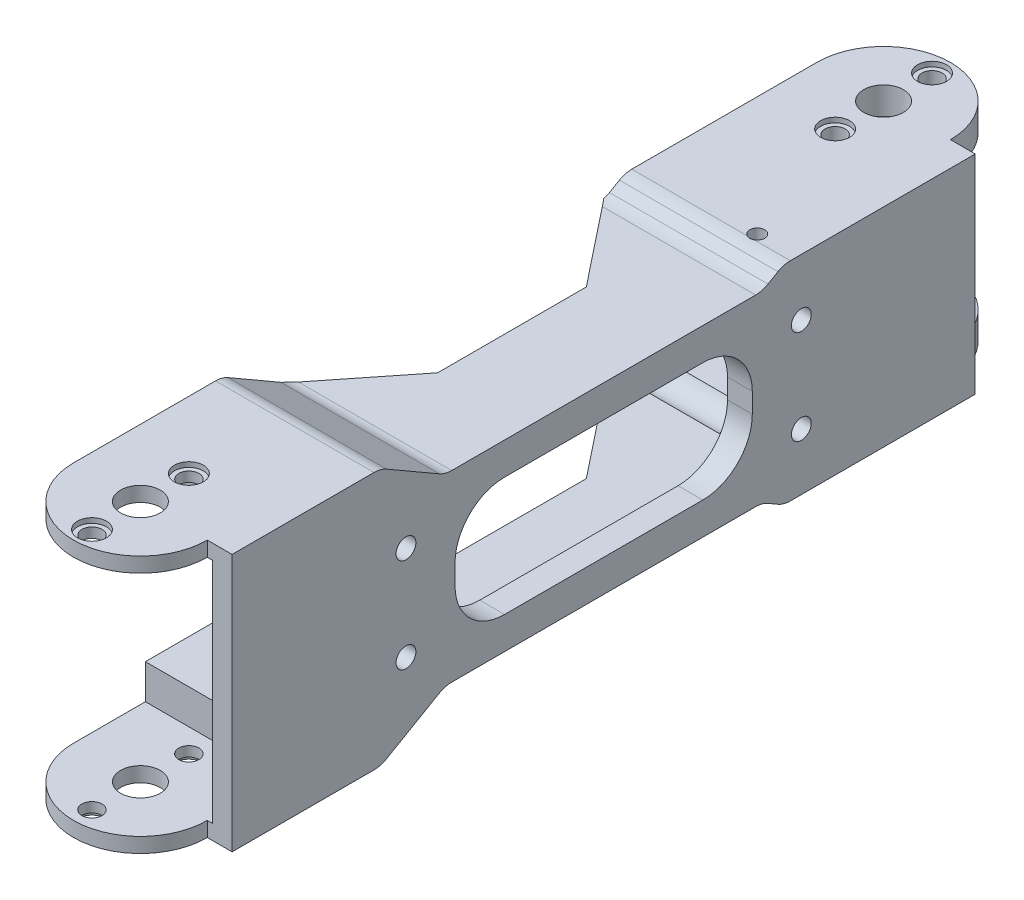
SolidWorks part; units mm, degrees
material "Custom Plastic"
ref_plane "Front Plane" through (0, 0, 0) normal (0, 0, 1) x (1, 0, 0)
ref_plane "Top Plane" through (0, 0, 0) normal (0, 1, 0) x (1, 0, 0)
ref_plane "Right Plane" through (0, 0, 0) normal (1, 0, 0) x (0, 0, -1)
sketch "Sketch1" plane through (0, 0, 0) normal (0, 1, 0) x (1, 0, 0)
  line L0 (0, 75) -> (0, -75) construction
  line L2 (-13.5, 75) -> (-13.5, -75)
  line L4 (13.5, 75) -> (13.5, -75)
  arc A0 (13.5, 75) -> (-13.5, 75) centre (0, 75) ccw
  arc A1 (-13.5, -75) -> (13.5, -75) centre (0, -75) ccw
  point P5 (0, 0)
  dimension "D1" = 150
  dimension "D2" = 27
extrude "Boss-Extrude1" add sketch "Sketch1" along normal mid plane 52
sketch "Sketch3" plane through (-13.5, 0, 0) normal (-1, 0, 0) x (0, 0, 1)
  line L0 (-45, 26) -> (-32.0096, 18.5)
  line L1 (-75, 26) -> (75, 26) construction
  line L2 (-32.0096, 18.5) -> (32.0096, 18.5)
  line L3 (32.0096, 18.5) -> (45, 26)
  line L4 (45, 26) -> (-45, 26)
  line L5 (-75, 26) -> (-75, -26) construction
  point P6 (0, 18.5)
  point P7 (0, 26)
  dimension "D1" = 7.5
  dimension "D2" = 30
  dimension "D3" = 30
extrude "Cut-Extrude1" cut sketch "Sketch3" against normal through all both and the other way through all
mirror "Mirror1" about plane through (0, 0, 0) normal (0, 1, 0) of "Cut-Extrude1"
sketch "Sketch4" plane through (-13.5, 0, 0) normal (-1, 0, 0) x (0, 0, 1)
  line L0 (-88.5, 26) -> (-88.5, -26) construction
  line L1 (60.5, 23) -> (88.5, 23)
  line L2 (-88.5, 15) -> (-60.5, 15)
  line L3 (-88.5, 15) -> (-88.5, 9)
  line L4 (-88.5, 9) -> (-60.5, 9)
  line L5 (-60.5, 15) -> (-60.5, 9)
  line L6 (-88.5, -15) -> (-60.5, -15)
  line L7 (-88.5, -15) -> (-88.5, -9)
  line L8 (-88.5, -9) -> (-60.5, -9)
  line L9 (-60.5, -15) -> (-60.5, -9)
  line L10 (60.5, 23) -> (60.5, 17)
  line L11 (60.5, 17) -> (88.5, 17)
  line L12 (88.5, 23) -> (88.5, 17)
  line L13 (60.5, -17) -> (88.5, -17)
  line L14 (60.5, -17) -> (60.5, -23)
  line L15 (60.5, -23) -> (88.5, -23)
  line L16 (88.5, -17) -> (88.5, -23)
  line L18 (88.5, -26) -> (88.5, 26) construction
  line L19 (-60.5, 9) -> (-60.5, -9) construction
  line L20 (60.5, 17) -> (60.5, -17) construction
  point P20 (-60.5, 0)
  point P21 (60.5, 0)
  dimension "D1" = 28
  dimension "D2" = 6
  dimension "D3" = 18
  dimension "D4" = 34
extrude "Cut-Extrude2" cut sketch "Sketch4" against normal through all both
sketch "Sketch5" plane through (-13.5, 0, 0) normal (-1, 0, 0) x (0, 0, 1)
  line L1 (-88.5, 15) -> (60.5, 15)
  line L2 (-88.5, 15) -> (-88.5, -15)
  line L3 (-88.5, -15) -> (60.5, -15)
  line L5 (-88.5, -15) -> (-88.5, -26) construction
  line L6 (-60.5, 15) -> (-75, 15) construction
  line L7 (-75, -15) -> (-60.5, -15) construction
  line L8 (60.5, 15) -> (60.5, 23)
  line L9 (88.5, -23) -> (60.5, -23)
  line L10 (88.5, -23) -> (88.5, 23)
  line L11 (88.5, 23) -> (60.5, 23)
  line L12 (60.5, -23) -> (60.5, -15)
  line L13 (60.5, -17) -> (60.5, -23) construction
  line L15 (75, 23) -> (88.5, 23) construction
  line L16 (60.5, -23) -> (75, -23) construction
  line L17 (88.5, -17) -> (88.5, 17) construction
extrude "Cut-Extrude3" cut sketch "Sketch5" against normal offset from surface (22 mm away) 5 contours L2 L3 L12 L9 L10 L11 L8 L1 up to face at (13.5, 0, 0)
sketch "Sketch6" plane through (8.5, 0, 0) normal (-1, 0, 0) x (0, 0, 1)
  line L0 (60.5, -15) -> (-60.5, -15) construction
  line L1 (85.4881, 17) -> (60.5, 17)
  line L2 (85.4881, 17) -> (85.4881, -15)
  line L3 (85.4881, -15) -> (60.5, -15)
  line L4 (60.5, 17) -> (60.5, -15)
  line L5 (60.5, -15) -> (60.5, -23) construction
  line L7 (60.5, 17) -> (75, 17) construction
extrude "Cut-Extrude4" cut sketch "Sketch6" against normal through all
sketch "Sketch7" plane through (8.5, 0, 0) normal (-1, 0, 0) x (0, 0, 1)
  line L1 (-85.4881, 9) -> (-60.5, 9)
  line L2 (-85.4881, 9) -> (-85.4881, -9)
  line L3 (-85.4881, -9) -> (-60.5, -9)
  line L4 (-60.5, 9) -> (-60.5, -9)
extrude "Cut-Extrude5" cut sketch "Sketch7" against normal through all
hole_wizard "CBORE for #00 Binding Head Machine Screw1" positions "Sketch11" profile "Sketch12" counterbore size "#00" standard "ANSI Inch"
sketch "Sketch11" plane through (0, 26, 0) normal (0, 1, 0) x (1, 0, 0)
  line L0 (9.779, -75) -> (-9.779, -75) construction
  line L2 (0, -65.221) -> (0, -84.779) construction
  line L3 (0, 84.78) -> (0, 65.22) construction
  line L5 (-13.5, 75) -> (-13.5, 45) construction
  arc A0 (-13.5, -75) -> (13.5, -75) centre (0, -75) ccw construction
  arc A2 (13.5, 75) -> (-13.5, 75) centre (0, 75) ccw construction
  point P0 (0, -65.221)
  point P6 (0, -84.779)
  point P17 (0, -75)
  point P18 (0, -75)
  point P45 (0, 75)
  dimension "D1" = 19.558
  dimension "D2" = 19.56
sketch "Sketch12" plane through (0, 26, 65.221) normal (1, 0, 0) x (0, 0, 1)
  line L0 (0, 0) -> (0, 4.2209)
  line L1 (0, 4.2209) -> (2.032, 3)
  line L2 (2.032, 3) -> (2.032, 1)
  line L3 (2.032, 1) -> (2.921, 1)
  line L4 (2.921, 1) -> (2.921, 0)
  line L5 (2.921, 0) -> (0, 0)
  line L10 (0, 4.2209) -> (-2.032, 3) construction
  line L11 (0, -6.35) -> (0, 107.95) construction
  dimension "Hole Dia." = 4.064
  dimension "Hole Depth" = 3
  dimension "C'Bore Dia." = 5.842
  dimension "C'Bore Depth" = 1
  dimension "Drill Angle" = 118
mirror "Mirror5" about plane through (0, 0, 0) normal (0, 1, 0) of "CBORE for #00 Binding Head Machine Screw1"
sketch "Sketch13" plane through (0, -26, 0) normal (0, -1, 0) x (1, 0, 0)
  circle A0 centre (0, -75) radius 4
  arc A1 (-13.5, -75) -> (13.5, -75) centre (0, -75) ccw construction
  dimension "D1" = 8
extrude "Cut-Extrude6" cut sketch "Sketch13" against normal through all both and the other way through all
mirror "Mirror4" about plane through (0, 0, 0) normal (0, 0, 1) of "Cut-Extrude6"
sketch "Sketch14" plane through (13.5, 0, 0) normal (1, 0, 0) x (0, 0, -1)
  line L0 (-75, 26) -> (-75, 23)
  line L1 (-75, 23) -> (-60.5, 23)
  line L2 (-60.5, 23) -> (-60.5, -23)
  line L3 (-60.5, -23) -> (-75, -23)
  line L4 (-75, -23) -> (-75, -26)
  line L5 (-75, -26) -> (-45, -26)
  line L6 (-45, -26) -> (-32.0096, -18.5)
  line L7 (-32.0096, -18.5) -> (32.0096, -18.5)
  line L8 (32.0096, -18.5) -> (45, -26)
  line L12 (60.5, -15) -> (60.5, 15)
  line L13 (60.5, 15) -> (75, 15)
  line L14 (75, 15) -> (75, 26)
  line L15 (75, 26) -> (45, 26)
  line L16 (45, 26) -> (32.0096, 18.5)
  line L17 (32.0096, 18.5) -> (-32.0096, 18.5)
  line L18 (-32.0096, 18.5) -> (-45, 26)
  line L19 (-45, 26) -> (-75, 26)
  line L20 (60.5, -15) -> (75, -15)
  line L21 (75, -15) -> (75, -26)
  line L22 (75, -26) -> (45, -26)
extrude "Boss-Extrude2" add sketch "Sketch14" along normal blind 5
sketch "Sketch15" plane through (8.5, 0, 0) normal (-1, 0, 0) x (0, 0, 1)
  line L0 (-79, 15) -> (-71, 15) construction
  line L1 (-62.5, 15) -> (62.5, 15)
  line L2 (-62.5, 15) -> (-62.5, -15)
  line L3 (-62.5, -15) -> (62.5, -15)
  line L4 (62.5, 15) -> (62.5, -15)
  line L5 (-75, -15) -> (60.5, -15) construction
extrude "Cut-Extrude7" cut sketch "Sketch15" against normal blind 5 and the other way up to surface (22 mm away) other way up to face at (-13.5, -21.7, 12.1)
sketch "Sketch17" plane through (0, 0, 60.5) normal (0, 0, 1) x (1, 0, 0)
  line L0 (18.5, -26) -> (13.5, -26) construction
  line L1 (18.5, 26) -> (14.5, 26)
  line L2 (18.5, 26) -> (18.5, -26)
  line L3 (18.5, -26) -> (14.5, -26)
  line L4 (14.5, 26) -> (14.5, -26)
  dimension "D1" = 4
extrude "Boss-Extrude4" add sketch "Sketch17" along normal up to surface (14.5 mm away) up to face at (16, 24.5, 75)
sketch "Sketch19" plane through (18.5, 0, 0) normal (1, 0, 0) x (0, 0, -1)
  line L0 (-39.899, 9.525) -> (-39.899, -9.525) construction
  line L3 (-75, 26) -> (-75, -26) construction
  circle A0 centre (-39.899, 9.525) radius 2
  circle A1 centre (-39.899, -9.525) radius 2
  point P4 (-39.899, 0)
  dimension "D2" = 4
  dimension "D1" = 19.05
  dimension "D3" = 35.101
extrude "Cut-Extrude11" cut sketch "Sketch19" against normal blind 10
sketch "Sketch20" plane through (13.5, 0, 0) normal (-1, 0, 0) x (0, 0, 1)
  line L1 (-30, 12) -> (30, 12)
  line L2 (-30, 12) -> (-30, -12)
  line L3 (-30, -12) -> (30, -12)
  line L4 (30, 12) -> (30, -12)
  point P4 (30, 0)
  point P8 (0, -12)
  dimension "D1" = 60
  dimension "D2" = 24
extrude "Cut-Extrude10" cut sketch "Sketch20" against normal blind 10
sketch "Sketch23" plane through (0, -26, 0) normal (0, -1, 0) x (1, 0, 0)
  line L0 (18.5, -32.0096) -> (18.5, -45) construction
  circle A5 centre (10.5, -39) radius 1.5
  circle A7 centre (0, -75) radius 4 construction
  point P4 (0, 0)
  dimension "D1" = 3
  dimension "D2" = 8
  dimension "D3" = 36
extrude "Cut-Extrude13" cut sketch "Sketch23" against normal through all both and the other way through all
mirror "Mirror7" about plane through (0, 0, 0) normal (0, 0, 1) of "Cut-Extrude11"
sketch "Sketch21" plane through (0, 18.5, 0) normal (0, 1, 0) x (1, 0, 0)
  line L0 (-13.5, 32.0096) -> (0, 15)
  line L2 (0, 15) -> (0, -15)
  line L3 (0, -15) -> (-13.5, -32.0096)
  line L4 (-13.5, -32.0096) -> (-13.5, 32.0096)
  line L5 (18.5, 32.0096) -> (-13.5, 32.0096) construction
  point P4 (-13.5, 0)
  point P9 (0, 0)
  dimension "D1" = 30
extrude "Cut-Extrude12" cut sketch "Sketch21" against normal up to surface (37 mm away) up to face at (2.5, -18.5, 0)
sketch "Sketch22" plane through (0, 0, -60.5) normal (0, 0, -1) x (-1, 0, 0)
  line L1 (-18.5, 15) -> (-13.5, 15)
  line L2 (-18.5, 15) -> (-18.5, -15)
  line L3 (-18.5, -15) -> (-13.5, -15)
  line L4 (-13.5, 15) -> (-13.5, -15)
extrude "Boss-Extrude5" add sketch "Sketch22" along normal up to surface (14.5 mm away) up to face at (16, 20.5, -75)
sketch "Sketch25" plane through (0, -26, 0) normal (0, -1, 0) x (1, 0, 0)
  line L0 (-13.5, -75) -> (-13.5, -45) construction
  line L1 (18.5, -32.0096) -> (-13.5, -32.0096)
  line L2 (18.5, -32.0096) -> (18.5, -88.5)
  line L3 (18.5, -88.5) -> (-13.5, -88.5)
  line L4 (-13.5, -32.0096) -> (-13.5, -88.5)
  line L5 (18.5, -45) -> (18.5, -75) construction
  line L6 (18.5, -32.0096) -> (-13.5, -32.0096) construction
  arc A0 (-13.5, -75) -> (13.5, -75) centre (0, -75) ccw construction
extrude "Cut-Extrude15" cut sketch "Sketch25" against normal blind 5
mirror "Mirror8" about plane through (0, 0, 0) normal (0, 1, 0) of "Cut-Extrude15"
fillet "Fillet1" radius 5 8 edges at (2.5, -26, 45) (2.5, -18.5, 32.0096) (2.5, -18.5, -32.0096) (2.5, -21, -36.3397) (2.5, 18.5, -32.0096) (2.5, 26, 45) (2.5, 18.5, 32.0096) (2.5, 21, -36.3397)
fillet "Fillet2" radius 10 4 edges at (16, -12, -30) (16, 12, -30) (16, -12, 30) (16, 12, 30)
hole_wizard "CBORE for #00 Binding Head Machine Screw2" positions "Sketch28" profile "Sketch29" counterbore size "#00" standard "ANSI Inch"
sketch "Sketch28" plane through (0, 21, 0) normal (0, 1, 0) x (1, 0, 0)
  line L0 (0, 84.78) -> (0, 65.22) construction
  line L2 (-13.5, 37.6795) -> (-13.5, 75) construction
  arc A0 (13.5, 75) -> (-13.5, 75) centre (0, 75) ccw construction
  point P0 (0, 84.78)
  point P2 (0, 65.22)
  point P13 (0, 75)
  dimension "D1" = 19.56
sketch "Sketch29" plane through (0, 21, -84.78) normal (1, 0, 0) x (0, 0, 1)
  line L0 (0, 0) -> (0, 7.2209)
  line L1 (0, 7.2209) -> (2.032, 6)
  line L2 (2.032, 6) -> (2.032, 1)
  line L3 (2.032, 1) -> (2.921, 1)
  line L4 (2.921, 1) -> (2.921, 0)
  line L5 (2.921, 0) -> (0, 0)
  line L10 (0, 7.2209) -> (-2.032, 6) construction
  line L11 (0, -6.35) -> (0, 107.95) construction
  dimension "Hole Dia." = 4.064
  dimension "Hole Depth" = 6
  dimension "C'Bore Dia." = 5.842
  dimension "C'Bore Depth" = 1
  dimension "Drill Angle" = 118
mirror "Mirror9" about plane through (0, 0, 0) normal (0, 1, 0) of "CBORE for #00 Binding Head Machine Screw2"
sketch "Sketch30" plane through (-13.5, 0, 0) normal (-1, 0, 0) x (0, 0, 1)
  line L0 (-88.5, 15) -> (-75, 15) construction
  line L1 (-88.5, 15) -> (-59.6, 15)
  line L2 (-88.5, 15) -> (-88.5, 15.5)
  line L3 (-88.5, 15.5) -> (-59.6, 15.5)
  line L4 (-59.6, 15) -> (-59.6, 15.5)
  line L5 (-88.5, 21) -> (-88.5, 15) construction
  dimension "D1" = 0.5
  dimension "D2" = 28.9
extrude "Cut-Extrude17" cut sketch "Sketch30" against normal up to surface (27 mm away) up to face at (13.5, 9.525, -37.899)
mirror "Mirror10" about plane through (0, 0, 0) normal (0, 1, 0) of "Cut-Extrude17"
fillet "Fillet3" radius 2 2 edges at (13.5, -15, 0.45) (13.5, 15, 0.45)
sketch "Sketch31" plane through (-13.5, 0, 0) normal (-1, 0, 0) x (0, 0, 1)
  line L0 (-40, -13.5) -> (-40, 13.5) construction
  line L1 (-44, -13.5) -> (-44, 13.5)
  line L2 (-36, -13.5) -> (-36, 13.5)
  arc A0 (-44, -13.5) -> (-36, -13.5) centre (-40, -13.5) ccw
  arc A1 (-36, 13.5) -> (-44, 13.5) centre (-40, 13.5) ccw
  point P2 (-40, 0)
  dimension "D1" = 4
  dimension "D2" = 27
  dimension "D3" = 40
extrude "Cut-Extrude18" cut sketch "Sketch31" against normal offset from surface (19 mm away) 8 up to face at (13.5, 9.525, -37.899)
sketch "Sketch32" plane through (-13.5, 0, 0) normal (-1, 0, 0) x (0, 0, 1)
  line L0 (32.0096, -18.6828) -> (32.0096, -15) construction
  line L1 (75, 16) -> (32.0096, 16)
  line L2 (75, 16) -> (75, -16)
  line L3 (75, -16) -> (32.0096, -16)
  line L4 (32.0096, 16) -> (32.0096, -16)
  line L6 (32.0096, 0) -> (0, 0) construction
  line L7 (75, -23) -> (75, 23) construction
  dimension "D1" = 32
extrude "Cut-Extrude19" cut sketch "Sketch32" against normal up to surface (28 mm away) up to face at (14.5, 0, 67.75)
sketch "Sketch33" plane through (0, 0, 60.5) normal (0, 0, 1) x (1, 0, 0)
  line L1 (14.5, -23) -> (-13.5, -23)
  line L2 (14.5, -23) -> (14.5, -15)
  line L3 (14.5, -15) -> (-13.5, -15)
  line L4 (-13.5, -23) -> (-13.5, -15)
extrude "Cut-Extrude20" cut sketch "Sketch33" along normal blind 29
